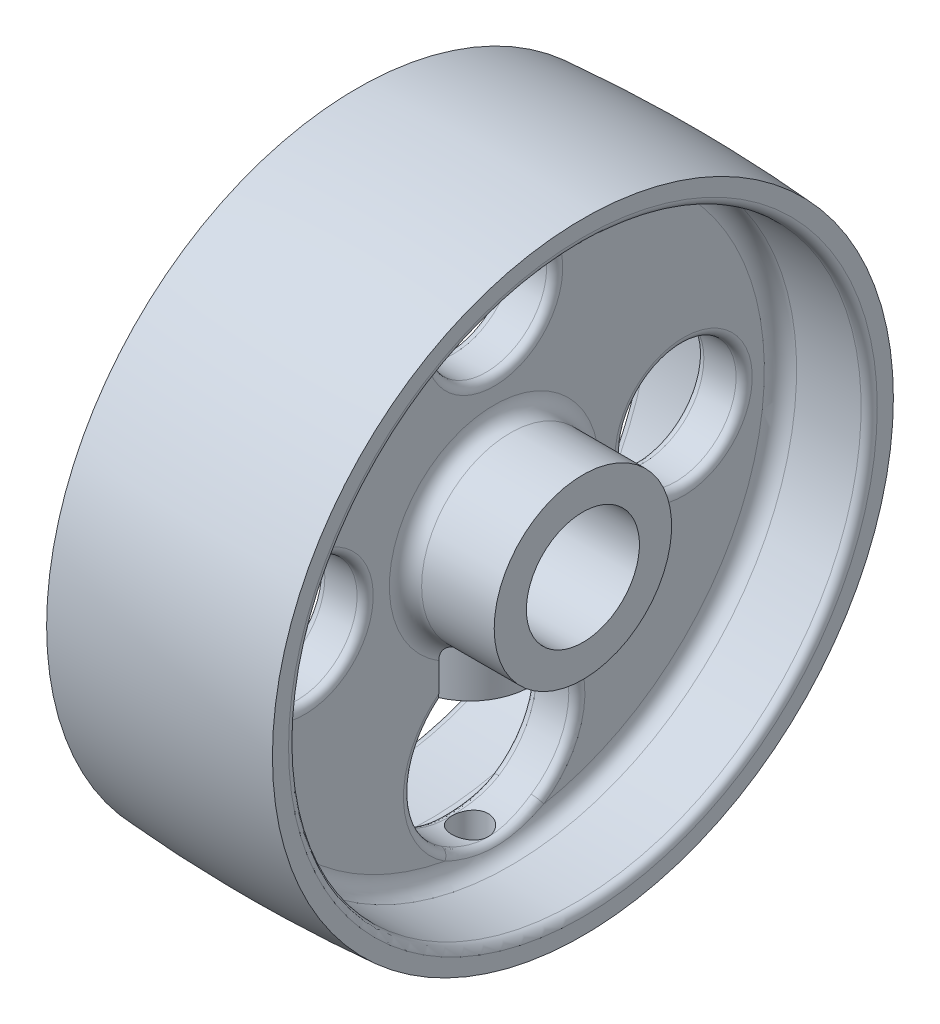
SolidWorks part; units mm, degrees
ref_plane "Front Plane" through (0, 0, 0) normal (0, 0, 1) x (1, 0, 0)
ref_plane "Top Plane" through (0, 0, 0) normal (0, 1, 0) x (1, 0, 0)
ref_plane "Right Plane" through (0, 0, 0) normal (1, 0, 0) x (0, 0, -1)
sketch "Sketch1" plane through (0, 0, 0) normal (0, 0, 1) x (1, 0, 0)
  line L0 (0, 0) -> (22.225, 0) construction
  line L2 (22.225, 11.1252) -> (22.225, 17.4625)
  line L3 (22.225, 17.4625) -> (7.9375, 17.4625)
  line L4 (4.7625, 20.6375) -> (4.7625, 53.1812)
  line L5 (7.9375, 56.3562) -> (20.6375, 56.3562)
  line L6 (22.225, 57.9438) -> (22.225, 61.1187)
  line L7 (0, 0) -> (0, 61.9125) construction
  line L8 (-22.225, 57.9438) -> (-22.225, 61.1187)
  line L9 (-7.9375, 56.3562) -> (-20.6375, 56.3562)
  line L10 (-4.7625, 20.6375) -> (-4.7625, 53.1812)
  line L11 (-22.225, 17.4625) -> (-7.9375, 17.4625)
  line L14 (-23.8125, 15.875) -> (-23.8125, 11.1252)
  line L15 (-23.8125, 11.1252) -> (22.225, 11.1252)
  line L16 (-23.8125, 15.875) -> (-22.225, 17.4625)
  arc A0 (-22.225, 61.1187) -> (22.225, 61.1187) centre (0, -249.6344) cw
  arc A1 (-7.9375, 56.3562) -> (-4.7625, 53.1812) centre (-7.9375, 53.1812) cw
  arc A2 (4.7625, 53.1812) -> (7.9375, 56.3562) centre (7.9375, 53.1812) cw
  arc A3 (7.9375, 17.4625) -> (4.7625, 20.6375) centre (7.9375, 20.6375) cw
  arc A4 (-4.7625, 20.6375) -> (-7.9375, 17.4625) centre (-7.9375, 20.6375) cw
  arc A5 (20.6375, 56.3562) -> (22.225, 57.9438) centre (20.6375, 57.9437) ccw
  arc A6 (-22.225, 57.9438) -> (-20.6375, 56.3562) centre (-20.6375, 57.9437) ccw
  point P20 (-4.7625, 56.3562)
  point P23 (4.7625, 56.3562)
  point P26 (4.7625, 17.4625)
  point P29 (-4.7625, 17.4625)
  point P31 (-23.8125, 17.4625)
  point P34 (22.225, 56.3562)
  point P37 (-22.225, 56.3562)
  dimension "D8" = 3.175
  dimension "D11" = 1.5875
  dimension "D1" = 22.225
  dimension "D2" = 11.1252
  dimension "D3" = 17.4625
  dimension "D4" = 9.525
  dimension "D5" = 61.9125
  dimension "D6" = 0.7937
  dimension "D7" = 4.7625
  dimension "D9" = 1.5875
  dimension "D10" = 45
  dimension "D12" = 46.0375
revolve "Revolve1" add sketch "Sketch1" angle 360 about L0
sketch "Sketch2" plane through (0, 0, 0) normal (1, 0, 0) x (0, 0, -1)
  line L0 (0, 61.9125) -> (0, -61.9125) construction
  circle A0 centre (0, 0) radius 61.9125 construction
  circle A1 centre (0, 37.3062) radius 11.9063
  circle A3 centre (37.3062, 0) radius 11.9063
  circle A4 centre (0, -37.3062) radius 11.9063 construction
  circle A5 centre (-37.3062, 0) radius 11.9063
  circle A6 centre (0, 0) radius 37.3063
  circle A7 centre (0, -37.3062) radius 16.2719
  point P19 (0, 0)
  dimension "D1" = 23.8125
  dimension "D2" = 74.6125
  dimension "D4" = 32.5437
  dimension "D3" = 4
extrude "Cut-Extrude2" cut sketch "Sketch2" against normal up to next and the other way up to next contours A6 A7 | A6 A7 | A3 A6 | A1 A6 | A6 A1 | A6 A3 | A5 A6 | A6 A5 region at (0, 42.0018, 0) region at (0, 31.9266, 0) region at (0, 0, 42.0018) region at (0, 0, 31.9266) region at (0, 0, -31.9266) region at (0, 0, -42.0018) region at (0, -29.8017, 0) region at (0, -43.5337, 0)
ref_plane "Plane1" through (0, -23.8125, 0) normal (0, 1, 0) x (1, 0, 0)
sketch "Sketch5" plane through (0, -23.8125, 0) normal (0, 1, 0) x (1, 0, 0)
  circle A0 centre (0, 0) radius 11.9062
  dimension "D1" = 23.8125
extrude "Boss-Extrude2" add sketch "Sketch5" along normal up to surface (11.0383 mm away) up to face at (7.9375, 0, 17.4625)
sketch "Sketch4" plane through (0, 0, 0) normal (0, 1, 0) x (1, 0, 0)
  circle A0 centre (0, 0) radius 3.5719
  dimension "D1" = 7.1437
extrude "Cut-Extrude3" cut sketch "Sketch4" against normal through all
fillet "Fillet1" radius 1.5875 12 edges at (-4.7625, -39.9632, 16.0535) (4.7625, -39.9632, 16.0535) (-4.7625, 0, 25.4) (-4.7625, 37.3062, -11.9063) (-4.7625, 0, -49.2125) (-4.7625, -39.9632, -16.0535) (4.7625, 0, 49.2125) (4.7625, 37.3062, 11.9063) (4.7625, 0, -25.4) (4.7625, -39.9632, -16.0535)
